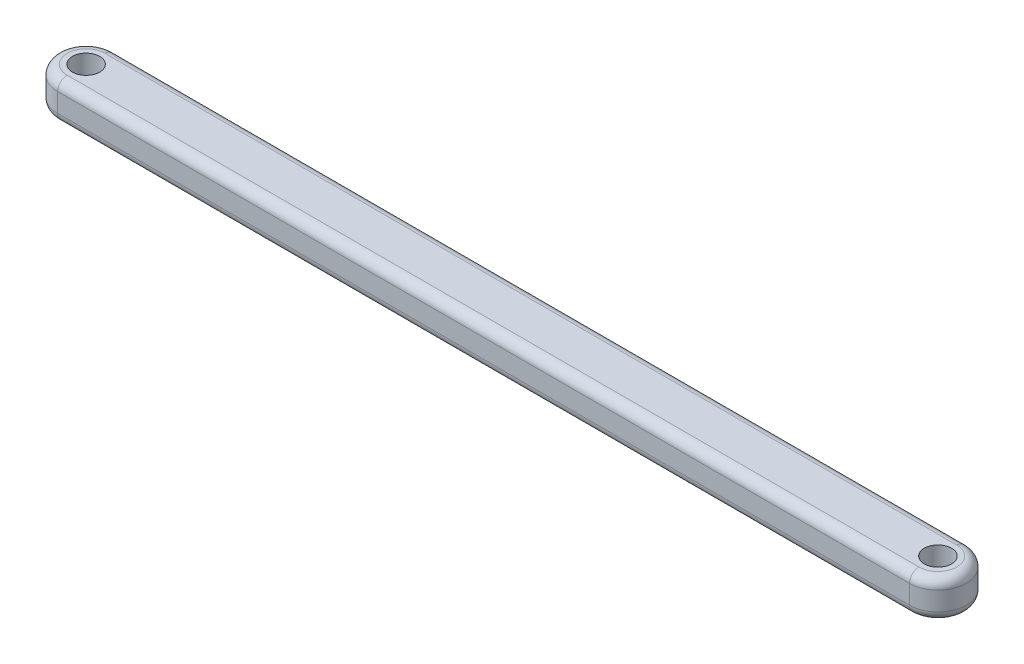
SolidWorks part; units mm, degrees
ref_plane "Front Plane" through (0, 0, 0) normal (0, 0, 1) x (1, 0, 0)
ref_plane "Top Plane" through (0, 0, 0) normal (0, 1, 0) x (1, 0, 0)
ref_plane "Right Plane" through (0, 0, 0) normal (1, 0, 0) x (0, 0, -1)
sketch "Sketch1" plane through (0, 0, 0) normal (0, 1, 0) x (1, 0, 0)
  line L0 (0, 0) -> (142.875, 0) construction
  line L1 (0, 4.7625) -> (142.875, 4.7625)
  line L2 (0, -4.7625) -> (142.875, -4.7625)
  arc A0 (0, 4.7625) -> (0, -4.7625) centre (0, 0) ccw
  arc A1 (142.875, -4.7625) -> (142.875, 4.7625) centre (142.875, 0) ccw
  point P3 (71.4375, 0)
  dimension "D1" = 142.875
  dimension "D2" = 9.525
extrude "Boss-Extrude1" add sketch "Sketch1" along normal mid plane 6.35
sketch "Sketch2" plane through (0, 3.175, 0) normal (0, 1, 0) x (1, 0, 0)
  circle A0 centre (0, 0) radius 2.286
  circle A1 centre (142.875, 0) radius 2.286
  dimension "D1" = 4.572
extrude "Cut-Extrude1" cut sketch "Sketch2" against normal through all
fillet "Fillet1" radius 1.5875 8 edges at (147.6375, -3.175, 0) (71.4375, -3.175, 4.7625) (-4.7625, -3.175, 0) (147.6375, 3.175, 0) (71.4375, 3.175, 4.7625) (-4.7625, 3.175, 0) (71.4375, -3.175, -4.7625) (71.4375, 3.175, -4.7625)
